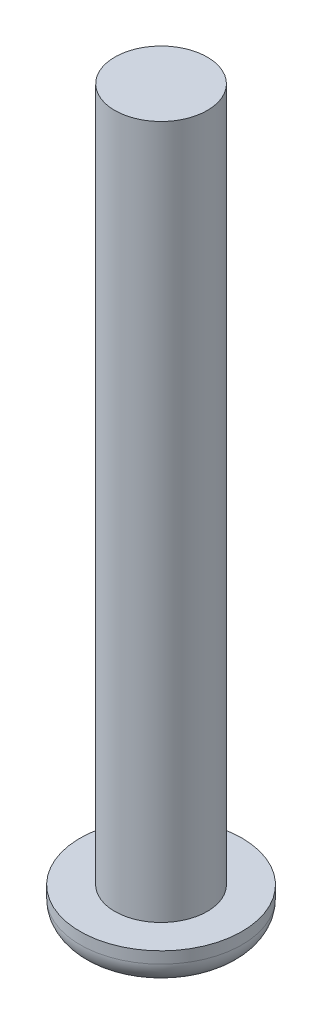
SolidWorks part; units mm, degrees
ref_plane "Front Plane" through (0, 0, 0) normal (0, 0, 1) x (1, 0, 0)
ref_plane "Top Plane" through (0, 0, 0) normal (0, 1, 0) x (1, 0, 0)
ref_plane "Right Plane" through (0, 0, 0) normal (1, 0, 0) x (0, 0, -1)
sketch "Sketch1" plane through (0, 0, 0) normal (0, 1, 0) x (1, 0, 0)
  circle A0 centre (0, 0) radius 4
  dimension "D1" = 8
extrude "Boss-Extrude1" add sketch "Sketch1" along normal blind 60 contours A0
sketch "Sketch2" plane through (0, 0, 0) normal (0, -1, 0) x (1, 0, 0)
  circle A0 centre (0, 0) radius 7
  circle A1 centre (0, 0) radius 4 construction
  circle A2 centre (0, 0) radius 4 construction
  dimension "D1" = 3
extrude "Boss-Extrude2" add sketch "Sketch2" along normal blind 3
fillet "Fillet1" radius 2 1 edges at (0, -3, -7)
sketch "Sketch3" plane through (0, -3, 0) normal (0, -1, 0) x (1, 0, 0)
  line L0 (0.375, 0.375) -> (1.5, 0.375)
  line L1 (-0.375, -1.5) -> (0.375, -1.5)
  line L2 (-0.375, -1.5) -> (-0.375, -0.375)
  line L3 (-0.375, 1.5) -> (0.375, 1.5)
  line L4 (0.375, -1.5) -> (0.375, -0.375)
  line L7 (-1.5, -0.375) -> (-0.375, -0.375)
  line L8 (-1.5, -0.375) -> (-1.5, 0.375)
  line L9 (-1.5, 0.375) -> (-0.375, 0.375)
  line L10 (1.5, -0.375) -> (1.5, 0.375)
  line L15 (0.375, 0.375) -> (0.375, 1.5)
  line L16 (0.375, -0.375) -> (1.5, -0.375)
  line L17 (-0.375, 0.375) -> (-0.375, 1.5)
  point P0 (0, 0)
  point P6 (0, 0)
  dimension "D1" = 3
  dimension "D2" = 0.75
extrude "Cut-Extrude1" cut sketch "Sketch3" against normal blind 1 draft 15
